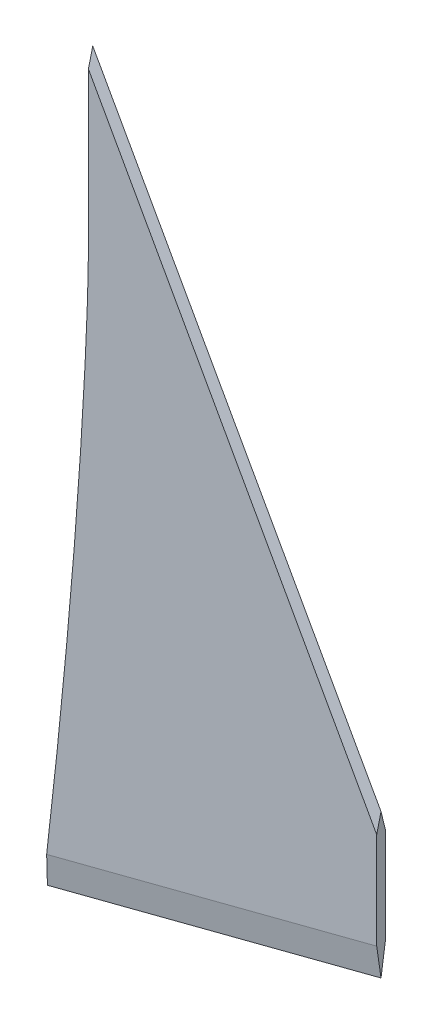
SolidWorks part; units mm, degrees
ref_plane "Front Plane" through (0, 0, 0) normal (0, 0, 1) x (1, 0, 0)
ref_plane "Top Plane" through (0, 0, 0) normal (0, 1, 0) x (1, 0, 0)
ref_plane "Right Plane" through (0, 0, 0) normal (1, 0, 0) x (0, 0, -1)
ref_plane "Plane1" through (0, 0, 1.5) normal (0, 0, 1) x (1, 0, 0)
sketch "Sketch2" plane through (0, 0, 1.5) normal (0, 0, 1) x (1, 0, 0)
  line L0 (76, 500) -> (76, 585.5789)
  line L1 (0, 0) -> (0, 585.5789)
  line L2 (0, 585.5789) -> (76, 585.5789)
  spline S0 degree 4 poles (0, 0) (0.0138, 0.0035) (0.0403, 0.0132) (0.0896, 0.0421) (0.1748, 0.1033) (0.2791, 0.1957) (0.3945, 0.3129) (0.5113, 0.4445) (0.662, 0.6264) (0.8743, 0.9054) (1.2103, 1.3931) (1.7479, 2.2715) (2.5811, 3.8159) (3.9077, 6.6298) (5.9906, 11.7322) (8.9748, 20.2155) (12.4921, 31.7245) (16.2812, 45.6068) (21.0209, 64.6514) (26.2066, 87.6584) (31.7463, 114.7224) (37.5379, 145.854) (42.8718, 177.0669) (47.8072, 208.3451) (52.3812, 239.6781) (56.6152, 271.0588) (60.5197, 302.4822) (63.6484, 330.0118) (66.1189, 353.6316) (68.0301, 373.3295) (69.4668, 389.0964) (70.8061, 404.872) (71.887, 418.6831) (72.7427, 430.5264) (73.4044, 440.3994) (73.9011, 448.3) (74.3048, 455.2148) (74.6268, 461.1432) (74.8778, 466.0844) (75.0676, 470.0378) (75.3363, 476.0055) (75.5634, 481.7365) (75.7481, 487.2308) (75.8847, 492.4881) (75.9403, 495.117) (75.978, 497.3706) (75.9936, 498.8731) (76, 499.6244) (76, 500) knots 0 0 0 0 0 0.000112 0.000223 0.000447 0.000827 0.001207 0.00152 0.001832 0.002688 0.003968 0.006183 0.009943 0.016507 0.028468 0.049587 0.080772 0.111303 0.141834 0.204204 0.266574 0.328944 0.391314 0.453684 0.516055 0.578425 0.640795 0.703165 0.73435 0.765535 0.79672 0.827905 0.85909 0.874683 0.890275 0.905868 0.92146 0.929257 0.937053 0.944849 0.952645 0.976323 0.982242 0.988161 0.994081 0.99704 1 1 1 1 1 construction
  spline S1 degree 4 poles (0, 0) (0.0138, 0.0035) (0.0403, 0.0132) (0.0896, 0.0421) (0.1748, 0.1033) (0.2791, 0.1957) (0.3945, 0.3129) (0.5113, 0.4445) (0.662, 0.6264) (0.8743, 0.9054) (1.2103, 1.3931) (1.7479, 2.2715) (2.5811, 3.8159) (3.9077, 6.6298) (5.9906, 11.7322) (8.9748, 20.2155) (12.4921, 31.7245) (16.2812, 45.6068) (21.0209, 64.6514) (26.2066, 87.6584) (31.7463, 114.7224) (37.5379, 145.854) (42.8718, 177.0669) (47.8072, 208.3451) (52.3812, 239.6781) (56.6152, 271.0588) (60.5197, 302.4822) (63.6484, 330.0118) (66.1189, 353.6316) (68.0301, 373.3295) (69.4668, 389.0964) (70.8061, 404.872) (71.887, 418.6831) (72.7427, 430.5264) (73.4044, 440.3994) (73.9011, 448.3) (74.3048, 455.2148) (74.6268, 461.1432) (74.8778, 466.0844) (75.0676, 470.0378) (75.3363, 476.0055) (75.5634, 481.7365) (75.7481, 487.2308) (75.8847, 492.4881) (75.9403, 495.117) (75.978, 497.3706) (75.9936, 498.8731) (76, 499.6244) (76, 500) knots 0 0 0 0 0 0.000112 0.000223 0.000447 0.000827 0.001207 0.00152 0.001832 0.002688 0.003968 0.006183 0.009943 0.016507 0.028468 0.049587 0.080772 0.111303 0.141834 0.204204 0.266574 0.328944 0.391314 0.453684 0.516055 0.578425 0.640795 0.703165 0.73435 0.765535 0.79672 0.827905 0.85909 0.874683 0.890275 0.905868 0.92146 0.929257 0.937053 0.944849 0.952645 0.976323 0.982242 0.988161 0.994081 0.99704 1 1 1 1 1
sketch "Sketch1" plane through (0, 0, 0) normal (0, 0, 1) x (1, 0, 0)
  line L1 (76, 560.99) -> (176, 380.99)
  line L2 (176, 380.99) -> (176, 330.99)
  line L3 (176, 330.99) -> (60.2723, 300.99)
  line L6 (76, 500) -> (76, 585.5789) construction
  line L7 (60.2723, 300.99) -> (0, 300.99)
  line L8 (0, 0) -> (0, 585.5789) construction
  line L9 (0, 300.99) -> (0, 560.99)
  line L10 (0, 560.99) -> (76, 560.99)
  spline S0 degree 4 poles (0, 0) (0.0138, 0.0035) (0.0403, 0.0132) (0.0896, 0.0421) (0.1748, 0.1033) (0.2791, 0.1957) (0.3945, 0.3129) (0.5113, 0.4445) (0.662, 0.6264) (0.8743, 0.9054) (1.2103, 1.3931) (1.7479, 2.2715) (2.5811, 3.8159) (3.9077, 6.6298) (5.9906, 11.7322) (8.9748, 20.2155) (12.4921, 31.7245) (16.2812, 45.6068) (21.0209, 64.6514) (26.2066, 87.6584) (31.7463, 114.7224) (37.5379, 145.854) (42.8718, 177.0669) (47.8072, 208.3451) (52.3812, 239.6781) (56.6152, 271.0588) (60.5197, 302.4822) (63.6484, 330.0118) (66.1189, 353.6316) (68.0301, 373.3295) (69.4668, 389.0964) (70.8061, 404.872) (71.887, 418.6831) (72.7427, 430.5264) (73.4044, 440.3994) (73.9011, 448.3) (74.3048, 455.2148) (74.6268, 461.1432) (74.8778, 466.0844) (75.0676, 470.0378) (75.3363, 476.0055) (75.5634, 481.7365) (75.7481, 487.2308) (75.8847, 492.4881) (75.9403, 495.117) (75.978, 497.3706) (75.9936, 498.8731) (76, 499.6244) (76, 500) knots 0 0 0 0 0 0.000112 0.000223 0.000447 0.000827 0.001207 0.00152 0.001832 0.002688 0.003968 0.006183 0.009943 0.016507 0.028468 0.049587 0.080772 0.111303 0.141834 0.204204 0.266574 0.328944 0.391314 0.453684 0.516055 0.578425 0.640795 0.703165 0.73435 0.765535 0.79672 0.827905 0.85909 0.874683 0.890275 0.905868 0.92146 0.929257 0.937053 0.944849 0.952645 0.976323 0.982242 0.988161 0.994081 0.99704 1 1 1 1 1 construction
  point P7 (176, 355.99)
  dimension "Tip Chord Length" = 50
  dimension "D4" = 30
  dimension "D5" = 300.99
  dimension "D1" = 260
  dimension "D2" = 100
extrude "Boss-Extrude1" add sketch "Sketch1" along normal blind 3
revolve "Cut-Revolve1" cut sketch "Sketch2" angle 360 about L1
chamfer "Chamfer6" distance 3 distance2 1.5 1 edges at (126, 470.99, 3)
chamfer "Chamfer7" distance 1.5 distance2 3 1 edges at (126, 470.99, 0)
chamfer "Chamfer8" distance 1.5 distance2 10 1 edges at (118.1362, 315.99, 3)
chamfer "Chamfer9" distance 10 distance2 1.5 1 edges at (118.1362, 315.99, 0)
equation "\"Fin Thickness\"= 3"
equation "\"Tip Chord Length\"= 50"
equation "\"Fin Width\"= 100"
equation "\"Taper Offset Distance from End\"= 30"
equation "\"Tip Chord Length@Sketch1\"= \"Tip Chord Length\""
equation "\"D1@Boss-Extrude1\"= \"Fin Thickness\""
equation "\"Leading Edge Taper Distance\"= 3"
equation "\"Trailing Edge Taper Distance\"= 10"
equation "\"D1@Chamfer6\"= \"Leading Edge Taper Distance\""
equation "\"D3@Chamfer6\"= \"Fin Thickness\" / 2"
equation "\"D3@Chamfer7\"= \"Leading Edge Taper Distance\""
equation "\"D1@Chamfer7\"= \"Fin Thickness\" / 2"
equation "\"D3@Chamfer8\"= \"Trailing Edge Taper Distance\""
equation "\"D1@Chamfer8\"= \"Fin Thickness\" / 2"
equation "\"D1@Chamfer9\"= \"Trailing Edge Taper Distance\""
equation "\"D3@Chamfer9\"= \"Fin Thickness\" / 2"
equation "\"D4@Sketch1\"= \"Taper Offset Distance from End\""
equation "\"Length of Reference Curve\"= 500"
equation "\"Radius of Reference Curve\"= 76"
equation "\"Root Chord Length\"= 260"
equation "\"D1@Sketch1\"= \"Root Chord Length\""
equation "\"D2@Sketch1\"= \"Fin Width\""
equation "\"D1@Plane1\"= \"Fin Thickness\" / 2"
